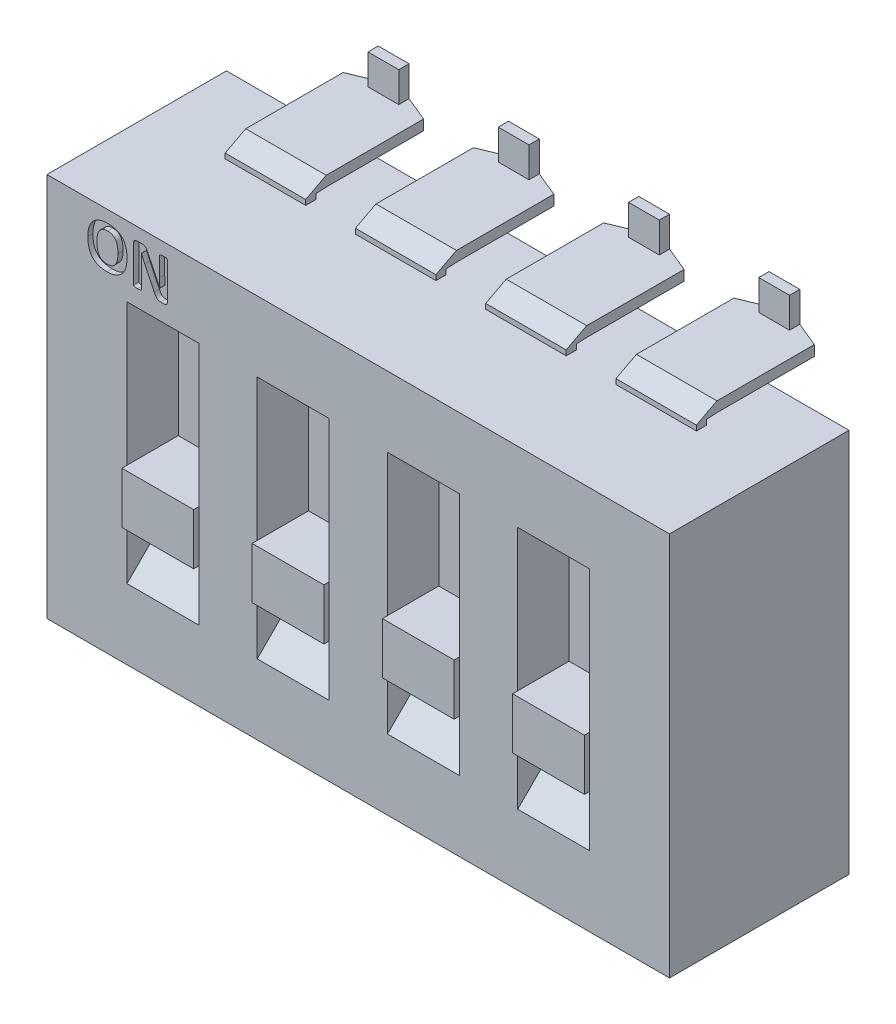
SolidWorks part; units mm, degrees
other "Детальный элемент1"
ref_plane "Спереди" through (0, 0, 0) normal (0, 0, 1) x (1, 0, 0)
ref_plane "Сверху" through (0, 0, 0) normal (0, 1, 0) x (1, 0, 0)
ref_plane "Справа" through (0, 0, 0) normal (1, 0, 0) x (0, 0, -1)
ref_plane "Плоскость1" through (0, 0, 1) normal (0, 0, 1) x (1, 0, 0)
sketch "Эскиз1" plane through (0, 0, 1) normal (0, 0, 1) x (1, 0, 0)
  line L1 (-6.07, -3.75) -> (6.07, -3.75)
  line L2 (-6.07, -3.75) -> (-6.07, 3.75)
  line L3 (-6.07, 3.75) -> (6.07, 3.75)
  line L4 (6.07, -3.75) -> (6.07, 3.75)
  line L5 (-6.07, -3.75) -> (6.07, 3.75) construction
  line L6 (-6.07, 3.75) -> (6.07, -3.75) construction
  point P0 (0, 0)
  dimension "D1" = 7.5
  dimension "D2" = 12.14
extrude "Бобышка-Вытянуть1" add sketch "Эскиз1" along normal blind 3.5
sketch "Эскиз2" plane through (0, -3.75, 0) normal (0, -1, 0) x (1, 0, 0)
  line L0 (-6.07, 1) -> (6.07, 1) construction
  line L1 (-4.595, 2.5) -> (-3.025, 2.5)
  line L2 (-4.595, 2.5) -> (-4.595, 2.3)
  line L3 (-4.595, 2.3) -> (-3.025, 2.3)
  line L4 (-3.025, 2.5) -> (-3.025, 2.3)
  line L5 (-4.595, 2.5) -> (-3.025, 2.3) construction
  line L6 (-4.595, 2.3) -> (-3.025, 2.5) construction
  line L7 (-6.07, 4.5) -> (-6.07, 1) construction
  point P0 (-3.81, 2.4)
  dimension "D1" = 1.57
  dimension "D2" = 0.2
  dimension "D3" = 1.4
  dimension "D4" = 2.26
extrude "Бобышка-Вытянуть2" add sketch "Эскиз2" along normal blind 0.1 separate body
sketch "Эскиз3" plane through (0, 0, 0) normal (0, 0, 1) x (1, 0, 0)
  line L1 (-4.11, -3.86) -> (-3.51, -3.86)
  line L2 (-4.11, -3.86) -> (-4.11, -4.65)
  line L3 (-4.11, -4.65) -> (-3.51, -4.65)
  line L4 (-3.51, -3.86) -> (-3.51, -4.65)
  line L5 (-4.11, -3.86) -> (-3.51, -4.65) construction
  line L6 (-4.11, -4.65) -> (-3.51, -3.86) construction
  point P0 (-3.81, -4.255)
  dimension "D1" = 0.6
  dimension "D2" = 0.79
  dimension "D3" = 4.65
extrude "Бобышка-Вытянуть3" add sketch "Эскиз3" along normal blind 0.2 separate body
sketch "Эскиз4" plane through (0, 0, 0.2) normal (0, 0, 1) x (1, 0, 0)
  line L0 (-3.51, -3.86) -> (-4.11, -3.86) construction
  line L1 (-4.595, -3.86) -> (-3.025, -3.86)
  line L2 (-4.595, -3.86) -> (-4.595, -4.06)
  line L3 (-4.595, -4.06) -> (-3.025, -4.06)
  line L4 (-3.025, -3.86) -> (-3.025, -4.06)
  dimension "D1" = 0.2
extrude "Бобышка-Вытянуть4" add sketch "Эскиз4" along normal offset from surface (1.9 mm away) 0.2 up to face at (-3.81, -3.8, 2.3)
chamfer "Фаска1" distance 0.2 distance2 0.485 2 edges at (-3.51, -3.96, 0.2) (-4.11, -3.96, 0.2) first distance on face at (-3.51, -4.216, 0.12) first distance on face at (-4.11, -4.216, 0.12)
loft "По сечениям1" add section face at (-3.81, -3.85, 2.4) section face at (-3.81, -3.96, 2.1) connector at (-3.025, -3.85, 2.5) connector at (-3.025, -4.06, 2.1)
sketch "Эскиз5" plane through (0, 0, 4.5) normal (0, 0, 1) x (1, 0, 0)
  line L5 (-4.51, 1.38) -> (-3.11, 1.38)
  line L6 (-4.51, 1.38) -> (-4.51, -1.38)
  line L7 (-4.51, -1.38) -> (-3.11, -1.38)
  line L8 (-3.11, 1.38) -> (-3.11, -1.38)
  line L9 (-4.51, 1.38) -> (-3.11, -1.38) construction
  line L10 (-4.51, -1.38) -> (-3.11, 1.38) construction
  point P0 (-3.81, 0)
  dimension "D1" = 2.76
  dimension "D2" = 1.4
extrude "Вырез-Вытянуть1" cut sketch "Эскиз5" against normal blind 1
chamfer "Фаска2" distance 1 angle 45 2 edges at (-3.81, 1.38, 4.5) (-3.81, -1.38, 4.5)
sketch "Эскиз6" plane through (0, 0, 3.5) normal (0, 0, 1) x (1, 0, 0)
  line L0 (-3.11, -1.38) -> (-3.11, 1.38) construction
  line L1 (-4.51, -1.38) -> (-3.11, -1.38)
  line L2 (-4.51, -1.38) -> (-4.51, -0.38)
  line L3 (-4.51, -0.38) -> (-3.11, -0.38)
  line L4 (-3.11, -1.38) -> (-3.11, -0.38)
  dimension "D1" = 1
extrude "Бобышка-Вытянуть5" add sketch "Эскиз6" along normal blind 1.1 separate body
mirror "Зеркальное отражение1" about plane through (0, 0, 0) normal (0, 1, 0) of bodies 111
pattern_linear "Линейный массив3" count 4 spacing 2.54 along (1, 0, 0) of "Вырез-Вытянуть1", "Фаска2"
pattern_linear "Линейный массив1" count 4 spacing 2.54 along (1, 0, 0) of bodies 120 111 113
sketch "Эскиз7" plane through (0, 0, 4.5) normal (0, 0, 1) x (1, 0, 0)
  text T0 "ON" font "Calibri" height 0.8
extrude "Вырез-Вытянуть2" cut sketch "Эскиз7" against normal blind 0.1
equation "\"N\"= 4"
equation "\"D2@Эскиз1\"=\"N\"*2.54+1.98"
equation "\"D1@Линейный массив1\"=\"N\""
equation "\"D1@Линейный массив2\"=\"N\""
equation "\"D1@Линейный массив3\"=\"N\""
